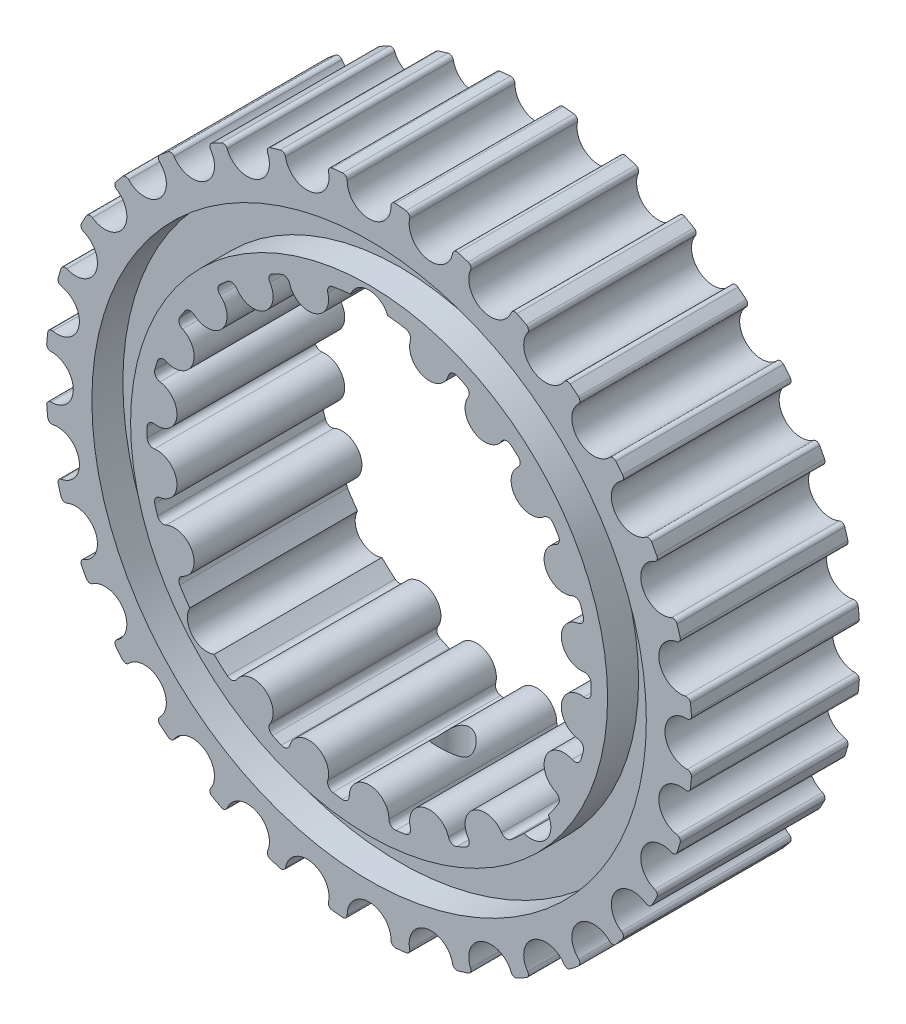
SolidWorks part; units mm, degrees
material "6061 Alloy"
ref_plane "Front Plane" through (0, 0, 0) normal (0, 0, 1) x (1, 0, 0)
ref_plane "Top Plane" through (0, 0, 0) normal (0, 1, 0) x (1, 0, 0)
ref_plane "Right Plane" through (0, 0, 0) normal (1, 0, 0) x (0, 0, -1)
sketch "Sketch1" plane through (0, 0, 0) normal (0, 0, 1) x (1, 0, 0)
  line L3 (3.27, 26.8516) -> (0, 0) construction
  line L4 (-3.8496, 26.7747) -> (0, 0) construction
  line L5 (3.8496, 26.7747) -> (0, 0) construction
  line L6 (-3.8858, 27.0261) -> (-3.9864, 27.7262)
  line L7 (3.8858, 27.0261) -> (3.9864, 27.7262)
  line L8 (-2.6956, 26.3433) -> (-2.6997, 31.2639) construction
  line L9 (2.6956, 26.3433) -> (2.6997, 31.195) construction
  circle A1 centre (0, 0) radius 28.0113 construction
  circle A2 centre (0, 0) radius 26.4809 construction
  arc A3 (-2.6956, 26.3433) -> (2.6956, 26.3433) centre (0, 26.3456) ccw construction
  arc A4 (2.6956, 26.3433) -> (3.27, 26.8516) centre (3.2081, 26.3429) cw construction
  arc A5 (-2.6956, 26.3433) -> (-3.27, 26.8516) centre (-3.2081, 26.3429) ccw construction
  arc A6 (-3.27, 26.8516) -> (-3.8496, 26.7747) centre (0, 0) ccw construction
  arc A7 (3.27, 26.8516) -> (3.8496, 26.7747) centre (0, 0) cw construction
  arc A8 (-3.9864, 27.7262) -> (3.9864, 27.7262) centre (0, 0) cw
  circle A9 centre (0, 0) radius 23.65 construction
  arc A10 (3.3007, 27.1038) -> (3.8858, 27.0261) centre (0, 0) cw
  arc A11 (2.4416, 26.3436) -> (3.3007, 27.1038) centre (3.2081, 26.3429) cw
  arc A12 (-2.4416, 26.3436) -> (2.4416, 26.3436) centre (0, 26.3456) ccw
  arc A13 (-2.4416, 26.3436) -> (-3.3007, 27.1038) centre (-3.2081, 26.3429) ccw
  arc A14 (-3.3007, 27.1038) -> (-3.8858, 27.0261) centre (0, 0) ccw
  point P1 (-3.9864, 27.7262)
  point P8 (0, 28.0113)
  point P9 (-2.6956, 26.3433)
  point P10 (2.6956, 26.3433)
  point P21 (-3.3657, 23.4093)
  point P22 (0, 23.65)
  dimension "D4" = 5.3912
  dimension "D1" = 47.3
  dimension "D8" = 56.0226
  dimension "D6" = 16.364
  dimension "D9" = 3.4
  dimension "D10" = 27.05
  dimension "D2" = 0.9613
  dimension "D5" = 0.096
  dimension "D3" = 0.254
extrude "Boss-Extrude1" add sketch "Sketch1" along normal mid plane 20.6375
ref_axis "Axis1" through (0, 0, 11.3506) along (0, 0, -1)
pattern_circular "CirPattern2" count 22 over 360 about axis through (0, 0, 11.3506) along (0, 0, -1) of "Boss-Extrude1"
sketch "Sketch2" plane through (0, 0, 0) normal (0, 0, 1) x (1, 0, 0)
  circle A0 centre (0, 0) radius 13
  dimension "D1" = 26
extrude "Boss-Extrude2" [suppressed] add sketch "Sketch2" along normal mid plane 20.6375 separate body
sketch "Sketch4" plane through (0, 0, 0) normal (0, 0, 1) x (1, 0, 0)
  line L0 (-3.8994, 39.5908) -> (-2.7456, 27.8764)
  line L1 (2.7456, 27.8764) -> (3.8994, 39.5908)
  line L2 (0, 40.7437) -> (0, 36.3824) construction
  line L3 (-3.8496, 26.7747) -> (-3.3657, 23.4093) construction
  circle A0 centre (0, 0) radius 40.7437 construction
  arc A1 (-2.6951, 39.129) -> (2.6951, 39.129) centre (0, 39.078) ccw
  arc A2 (-2.6956, 26.3433) -> (2.6956, 26.3433) centre (0, 26.3456) ccw construction
  circle A3 centre (0, 0) radius 28.0113 construction
  arc A4 (2.7456, 27.8764) -> (-2.7456, 27.8764) centre (0, 0) ccw
  arc A5 (-2.6951, 39.129) -> (-3.2493, 39.6495) centre (-3.2075, 39.1387) ccw
  arc A6 (-3.8994, 39.5908) -> (-3.2493, 39.6495) centre (0, 0) cw
  arc A7 (0, 36.3824) -> (-3.5661, 36.2072) centre (0, 0) ccw construction
  arc A8 (3.8994, 39.5908) -> (3.2493, 39.6495) centre (0, 0) ccw
  arc A9 (3.2493, 39.6495) -> (2.6951, 39.129) centre (3.2075, 39.1387) ccw
  arc A10 (-2.6956, 26.3433) -> (-3.27, 26.8516) centre (-3.2081, 26.3429) ccw construction
  point P26 (0, 36.3824)
  point P47 (-3.9936, 40.5475)
  dimension "D2" = 11.25
  dimension "D4" = 3.4
  dimension "D3" = 3.4
  dimension "D5" = 0.9613
  dimension "D6" = 0.9613
extrude "Boss-Extrude3" add sketch "Sketch4" against normal up to surface and the other way up to surface up to face at (-28.0113, 0, -10.3187) other way up to face at (-28.0113, 0, 10.3187)
pattern_circular "CirPattern3" count 32 over 360 about axis through (0, 0, 11.3506) along (0, 0, -1) of "Boss-Extrude3" reverse direction yes
sketch "Sketch7" plane through (0, 0, 10.3187) normal (0, 0, 1) x (1, 0, 0)
  line L0 (0, 27.05) -> (0, 36.3824) construction
  line L1 (0, 34.0975) -> (0, 29.335) construction
  circle A0 centre (0, 0) radius 34.0975
  circle A1 centre (0, 0) radius 29.335
  arc A3 (-3.27, 26.8516) -> (-3.8496, 26.7747) centre (0, 0) ccw construction
  point P4 (0, 34.0975)
  point P5 (0, 29.335)
  point P6 (0, 27.05)
  point P11 (0, 31.7162)
  dimension "D1" = 4.7625
extrude "Cut-Extrude2" cut sketch "Sketch7" against normal blind 3.81
pattern_circular "CirPattern6" [suppressed] count 8 over 360 about axis through (0, 0, 11.3506) along (0, 0, -1) of bodies 110
sketch "Sketch11" plane through (0, 0, 10.3187) normal (0, 0, 1) x (1, 0, 0)
  arc A2 (3.3007, 27.1038) -> (2.4416, 26.3436) centre (3.2081, 26.3429) ccw construction
  arc A3 (-2.4416, 26.3436) -> (2.4416, 26.3436) centre (0, 26.3456) ccw construction
  arc A4 (-2.4416, 26.3436) -> (-3.3007, 27.1038) centre (-3.2081, 26.3429) ccw construction
  arc A9 (3.3007, 27.1038) -> (2.4416, 26.3436) centre (3.2081, 26.3429) ccw
  arc A13 (-2.2841, 27.2083) -> (2.2841, 27.2083) centre (0, 26.3456) cw
  arc A14 (-2.2841, 27.2083) -> (-3.3007, 27.1038) centre (0, 0) ccw
  arc A15 (-2.4416, 26.3436) -> (2.4416, 26.3436) centre (0, 26.3456) ccw
  arc A16 (-2.4416, 26.3436) -> (-3.3007, 27.1038) centre (-3.2081, 26.3429) ccw
  arc A17 (-3.3007, 27.1038) -> (-4.469, 26.9358) centre (0, 0) ccw construction
  arc A18 (3.3007, 27.1038) -> (2.2841, 27.2083) centre (0, 0) ccw
  arc A19 (4.469, 26.9358) -> (3.3007, 27.1038) centre (0, 0) ccw construction
extrude "Cut-Extrude3" cut sketch "Sketch11" against normal through all both and the other way through all
pattern_circular "CirPattern9" count 11 over 360 about axis through (0, 0, 11.3506) along (0, 0, -1) skipping 1, 2, 3, 5, 6, 8, 9, 10 of "Cut-Extrude3"
hole_wizard "#10-32 Tapped Hole1" positions "Sketch13" profile "Sketch15" tap size "#10-32" standard "ANSI Inch" end condition through all
sketch "Sketch13" plane through (0, 0, 0) normal (0, 1, 0) x (1, 0, 0)
  point P0 (0, 0)
sketch "Sketch15" plane through (0, 0, 0) normal (1, 0, 0) x (0, 0, 1)
  line L0 (0, 0) -> (0, 39.6512)
  line L1 (0, 39.6512) -> (2.0193, 39.6512)
  line L2 (2.0193, 39.6512) -> (2.0193, 0)
  line L5 (2.0193, 0) -> (0, 0)
  line L11 (0, -6.35) -> (0, 107.95) construction
  dimension "Thru Tap Drill Dia." = 4.0386
  dimension "Thru Tap Drill Depth" = 39.6512
cosmetic thread "Hole Thread1" parameters "D2"=4.826
equation "\"pitch\"=0.314961"
equation "\"D6@Sketch1\"=360/22"
equation "\"D8@Sketch1\"=\"pitch\"*22/pi"
equation "\"D1@Sketch4\" = \"pitch\" * \"teeth\" / pi"
equation "\"teeth\"= 32"
equation "\"D2@Sketch4\"=360/\"teeth\""
equation "\"D1@CirPattern3\"=\"teeth\""
